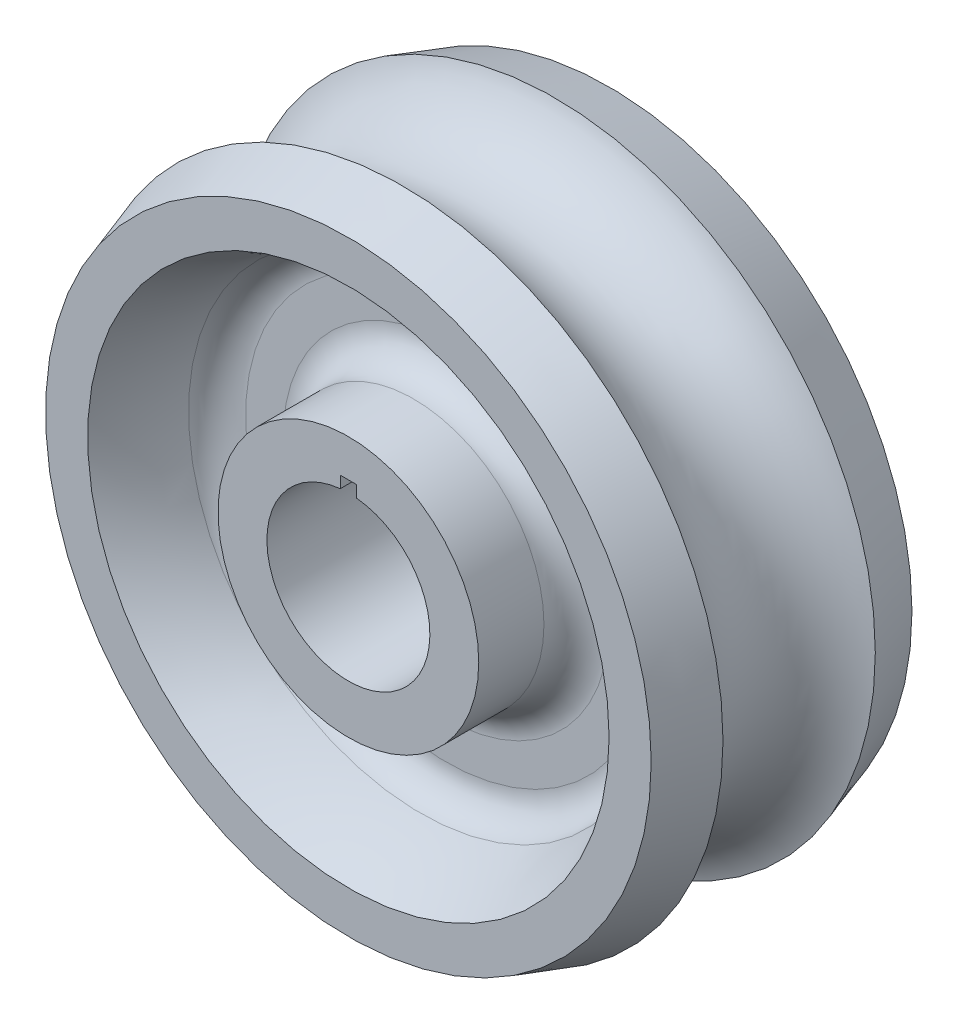
SolidWorks part; units mm, degrees
material "PW20:29:Sc:0:"
ref_plane "Front" through (0, 0, 0) normal (0, 0, 1) x (1, 0, 0)
ref_plane "Top" through (0, 0, 0) normal (0, 1, 0) x (1, 0, 0)
ref_plane "Right" through (0, 0, 0) normal (1, 0, 0) x (0, 0, -1)
other "Configuration Table"
sketch "Sketch1" plane through (0, 0, 0) normal (1, 0, 0) x (0, 0, -1)
  line L0 (0, 0) -> (159.8623, 0) construction
  line L1 (0, 0) -> (0, 93.2897) construction
  line L2 (-12.7, 7.9375) -> (12.7, 7.9375)
  line L3 (12.7, 7.9375) -> (12.7, 12.7)
  line L4 (12.7, 12.7) -> (6.35, 12.7)
  line L5 (3.175, 15.875) -> (3.175, 19.5365)
  line L6 (12.7, 25.4) -> (12.7, 29.5021)
  line L7 (12.7, 29.5021) -> (7.4182, 31.2134)
  line L8 (-12.7, 29.5021) -> (-7.4182, 31.2134)
  line L9 (-12.7, 25.4) -> (-12.7, 29.5021)
  line L10 (-3.175, 15.875) -> (-3.175, 19.5365)
  line L11 (-12.7, 12.7) -> (-6.35, 12.7)
  line L12 (-12.7, 7.9375) -> (-12.7, 12.7)
  arc A0 (6.35, 12.7) -> (3.175, 15.875) centre (6.35, 15.875) cw
  arc A1 (3.175, 19.5365) -> (5.6444, 22.6321) centre (6.35, 19.5365) cw
  arc A2 (5.6444, 22.6321) -> (12.7, 25.4) centre (0, 47.397) ccw
  arc A3 (7.4182, 31.2134) -> (-7.4182, 31.2134) centre (0, 33.6169) cw
  arc A4 (-5.6444, 22.6321) -> (-12.7, 25.4) centre (0, 47.397) cw
  arc A5 (-3.175, 19.5365) -> (-5.6444, 22.6321) centre (-6.35, 19.5365) ccw
  arc A6 (-6.35, 12.7) -> (-3.175, 15.875) centre (-6.35, 15.875) ccw
  point P29 (0, 7.9375)
  dimension "D1" = 25.4
  dimension "D2" = 3.175
  dimension "D4" = 7.7978
  dimension "D9" = 25.4
  dimension "D3" = 50.8
  dimension "D5" = 6.35
  dimension "D6" = 4.7625
  dimension "D7" = 15.875
  dimension "D8" = 21.5646
  dimension "D10" = 67.2338
revolve "Base-Revolve" add sketch "Sketch1" angle 360 about L0
sketch "Sketch2" plane through (0, 0, 12.7) normal (0, 0, 1) x (1, 0, 0)
  line L0 (0, 0) -> (0, 10.5711) construction
  line L1 (-0.7937, 7.8977) -> (-0.7937, 9.0424)
  line L2 (0.7937, 7.8977) -> (0.7937, 9.0424)
  line L3 (-0.7937, 9.0424) -> (0.7937, 9.0424)
  circle A0 centre (0, 0) radius 7.9375 construction
  arc A1 (0.7937, 7.8977) -> (-0.7937, 7.8977) centre (0, 0) ccw
  dimension "D1" = 1.5875
  dimension "D2" = 9.0424
extrude "Cut-Extrude1" cut sketch "Sketch2" against normal through all
ref_axis "Worm CL" through (0, 0, 50) along (0, 0, -1)
